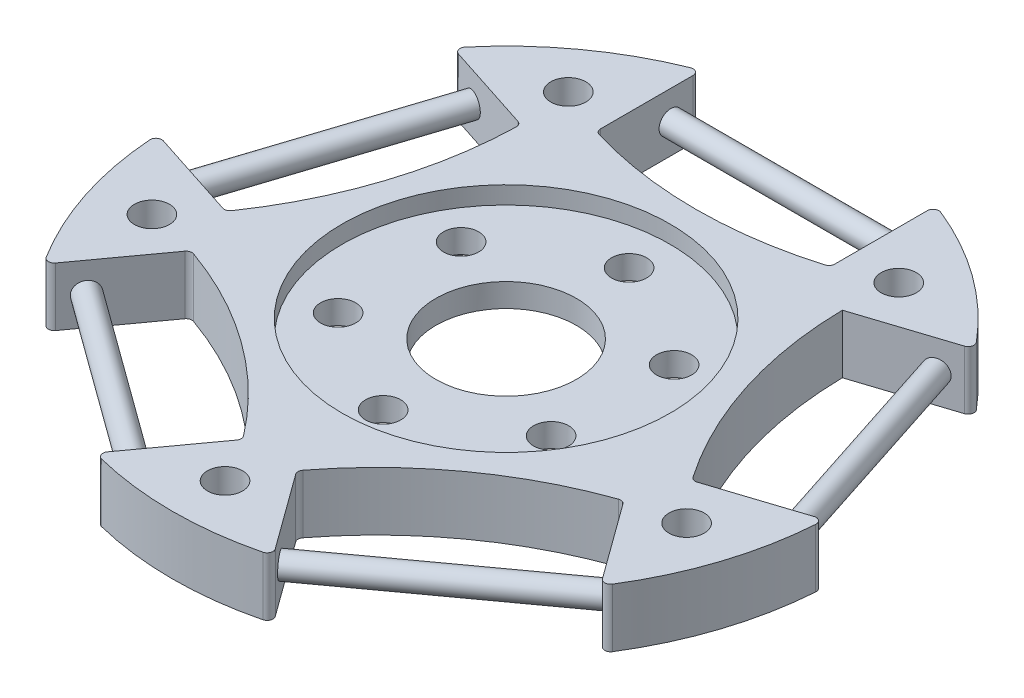
SolidWorks part; units mm, degrees
other "Camera1"
ref_plane "Front Plane" through (0, 0, 0) normal (0, 0, 1) x (1, 0, 0)
ref_plane "Top Plane" through (0, 0, 0) normal (0, 1, 0) x (1, 0, 0)
ref_plane "Right Plane" through (0, 0, 0) normal (1, 0, 0) x (0, 0, -1)
sketch "Sketch1" plane through (0, 0, 0) normal (0, 1, 0) x (1, 0, 0)
  line L0 (0, 0) -> (0, 50000) construction
  line L1 (0, 0) -> (-50000, 0) construction
  circle A0 centre (0, 0) radius 28.5
  dimension "D1" = 57
extrude "Boss-Extrude1" add sketch "Sketch1" along normal blind 5
sketch "Sketch2" plane through (0, 5, 0) normal (0, 1, 0) x (1, 0, 0)
  line L0 (0, 0) -> (13.4182, 0) construction
  line L1 (0, 0) -> (0, 50000) construction
  line L2 (10, 26.688) -> (10, 17.688)
  line L3 (-10, 26.688) -> (-10, 17.688)
  circle A0 centre (0, 0) radius 28.5 construction
  arc A1 (-10, 17.688) -> (10, 17.688) centre (0, 50.0973) ccw
  arc A2 (-10, 26.688) -> (10, 26.688) centre (0, 0) cw
  dimension "D1" = 9
  dimension "D2" = 10
extrude "Cut-Extrude1" cut sketch "Sketch2" against normal through all
pattern_circular "CirPattern1" count 5 over 360 about axis through (0, 5, 0) along (0, 1, 0) of "Cut-Extrude1"
sketch "Sketch3" plane through (0, 5, 0) normal (0, 1, 0) x (1, 0, 0)
  circle A0 centre (0, 0) radius 14
  dimension "D1" = 28
extrude "Cut-Extrude2" cut sketch "Sketch3" against normal blind 1.5
ref_plane "Plane1" through (0, 2.5, 0) normal (0, 1, 0) x (1, 0, 0)
mirror "Mirror1" about plane through (0, 2.5, 0) normal (0, 1, 0) of "Cut-Extrude2"
sketch "Sketch4" plane through (0, 3.5, 0) normal (0, 1, 0) x (1, 0, 0)
  circle A0 centre (0, 10.5) radius 1.5
  circle A1 centre (0, 0) radius 10.5 construction
  circle A2 centre (9.0933, 5.25) radius 1.5
  circle A3 centre (9.0933, -5.25) radius 1.5
  circle A4 centre (0, -10.5) radius 1.5
  circle A5 centre (-9.0933, -5.25) radius 1.5
  circle A6 centre (-9.0933, 5.25) radius 1.5
  circle A7 centre (0, 0) radius 6
  point P18 (0, 0)
  dimension "D2" = 3
  dimension "D4" = 12
  dimension "D1" = 10.5
  dimension "D3" = 6
extrude "Cut-Extrude3" cut sketch "Sketch4" against normal through all
sketch "Sketch5" plane through (0, 5, 0) normal (0, 1, 0) x (1, 0, 0)
  line L0 (0, 0) -> (0, -50000) construction
  circle A0 centre (0, -24) radius 1.5
  dimension "D1" = 24
extrude "Cut-Extrude4" cut sketch "Sketch5" against normal through all
pattern_circular "CirPattern2" count 5 over 360 about axis through (0, 3.5, 0) along (0, 1, 0) of "Cut-Extrude4"
fillet "Fillet1" radius 0.5 19 edges at (10, 2.5, -17.688) (-10, 2.5, -17.688) (-13.7321, 2.5, -14.9765) (-19.9125, 2.5, 4.0447) (-18.4869, 2.5, 8.4321) (-2.3066, 2.5, 20.1878) (19.9125, 2.5, 4.0447) (18.4869, 2.5, 8.4321) (2.3066, 2.5, 20.1878) (10, 2.5, -26.688) (22.2916, 2.5, -17.7576) (28.472, 2.5, 1.2635) (23.777, 2.5, 15.7132) (7.5967, 2.5, 27.4689) (-7.5967, 2.5, 27.4689) (-23.777, 2.5, 15.7132) (-28.472, 2.5, 1.2635) (-22.2916, 2.5, -17.7576) (-10, 2.5, -26.688)
sketch "Sketch7" plane through (-8.0902, 0, -5.8779) normal (0.809, 0, 0.5878) x (0.5878, 0, -0.809)
  line L1 (-33.8543, 2.5) -> (-18.0591, 2.5) construction
  line L3 (-18.0591, 0) -> (-18.0591, 5) construction
  line L5 (-22.0079, 10) -> (-22.0079, 0) construction
  line L7 (-18.0591, 0) -> (-25.9567, 0) construction
  circle A0 centre (-24.0591, 2.5) radius 1
  point P0 (-25.9567, 2.5)
  point P1 (-22.0079, 5)
  dimension "D1" = 2
  dimension "D2" = 6
extrude "Boss-Extrude2" add sketch "Sketch7" along normal up to next
pattern_circular "CirPattern3" count 5 over 360 about axis through (0, 3.5, 0) along (0, 1, 0) of "Boss-Extrude2"
